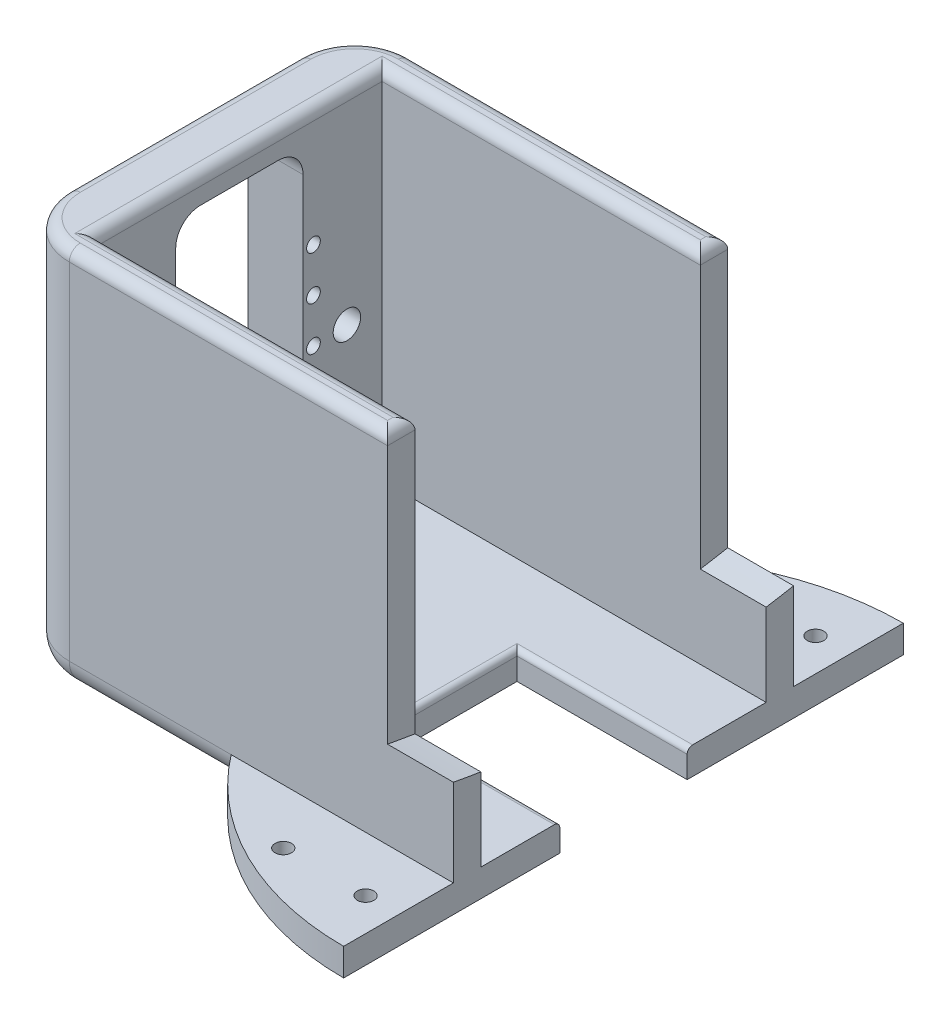
SolidWorks part; units mm, degrees
ref_plane "Plan de face" through (0, 0, 0) normal (0, 0, 1) x (1, 0, 0)
ref_plane "Plan de dessus" through (0, 0, 0) normal (0, 1, 0) x (1, 0, 0)
ref_plane "Plan de droite" through (0, 0, 0) normal (1, 0, 0) x (0, 0, -1)
sketch "Esquisse1" plane through (0, 0, 0) normal (0, 1, 0) x (1, 0, 0)
  line L0 (-50.0182, 0) -> (81.7007, 0) construction
  line L1 (-40.4969, 31) -> (0, 31)
  line L2 (-70, 26) -> (-40.4969, 26)
  line L3 (-70, 26) -> (-70, -26)
  line L4 (0, 31) -> (0, -31)
  line L5 (0, 68.3448) -> (0, -68.3448) construction
  line L6 (-40.4969, 31) -> (-80, 31)
  line L7 (-80, 31) -> (-80, -31)
  line L8 (-80, -31) -> (-40.4969, -31)
  line L9 (-70, -26) -> (-40.4969, -26)
  line L10 (-40.4969, 26) -> (0, 26)
  line L11 (-40.4969, -26) -> (0, -26)
  line L12 (-40.4969, -31) -> (0, -31)
  point P14 (-50, 0)
  dimension "D1" = 80
  dimension "D2" = 62
  dimension "D4" = 10
  dimension "D5" = 5
extrude "Boss.-Extru.5" add sketch "Esquisse1" along normal mid plane 100 contours L9 L3 L2 L6 L7 L8 region at (-20.2485, 0, -29.9879)
sketch "Esquisse5" plane through (-70, 0, 0) normal (1, 0, 0) x (0, 0, -1)
  line L1 (-11.6, -2) -> (11.6, -2)
  line L2 (-11.6, -2) -> (-11.6, -33.8)
  line L3 (-11.6, -33.8) -> (11.6, -33.8)
  line L4 (11.6, -2) -> (11.6, -33.8)
  line L5 (-11.6, -2) -> (-11.6, 5.5)
  line L6 (11.6, -2) -> (11.6, 5.5)
  line L7 (-7.1, 10) -> (7.1, 10)
  arc A0 (-11.6, 5.5) -> (-7.1, 10) centre (-7.1, 5.5) cw
  arc A1 (7.1, 10) -> (11.6, 5.5) centre (7.1, 5.5) cw
  circle A2 centre (0, 0) radius 2.15
  dimension "D3" = 4.3
  dimension "D6" = 4.5
  dimension "D7" = 4.5
  dimension "D1" = 2
  dimension "D2" = 11.6
  dimension "D4" = 43.8
  dimension "D5" = 23.2
  dimension "D8" = 12
extrude "Enlèv. mat.-Extru.1" cut sketch "Esquisse5" against normal blind 10 contours A2 L1 L6 A1 L7 A0 L5 | A2 L1 L2 L3 L4 | L1 A2 | L1 A2 region at (-70, 4.0537, 0) region at (-70, -17.9034, 0) region at (-70, 0.0228, 0) region at (-70, -2.0602, 0)
sketch "Esquisse8" plane through (0, -50, 0) normal (0, 1, 0) x (1, 0, 0)
  line L0 (0, -51) -> (0, 51)
  line L1 (-40.5, -31) -> (-80, -31)
  line L2 (-80, -31) -> (-80, 31)
  line L3 (-80, 31) -> (-40.5, 31)
  line L4 (0, -26) -> (0, -31) construction
  line L5 (-80, -31) -> (0, -31) construction
  line L6 (-80, 0) -> (-0.0031, 0) construction
  arc A1 (0, -51) -> (-40.5, -31) centre (-0.0031, 0) cw
  arc A3 (-40.5, 31) -> (0, 51) centre (-0.0031, 0) cw
  dimension "D1" = 51
  dimension "D2" = 51
  dimension "D3" = 40.5
  dimension "D4" = 20
extrude "Boss.-Extru.6" add sketch "Esquisse8" against normal blind 5
sketch "Esquisse9" plane through (0, 0, 0) normal (1, 0, 0) x (0, 0, -1)
  line L1 (31, 50) -> (31, -50) construction
  line L2 (-31, 50) -> (31, 50)
  line L3 (-31, 50) -> (-31, 15)
  line L4 (-31, 15) -> (31, 15)
  line L8 (0, -5.2261) -> (0, 54.1477) construction
  line L9 (31, 50) -> (31, 15)
  line L10 (-7.1, 10) -> (7.1, 10) construction
  dimension "D1" = 5
sketch "Esquisse11" plane through (-70, 0, 0) normal (1, 0, 0) x (0, 0, -1)
  line L0 (0, 0) -> (0, -23.2285) construction
  line L1 (-11.6, -2) -> (-11.6, -33.8) construction
  line L3 (26, -50) -> (-26, -50) construction
  circle A0 centre (-19.6, -22.214) radius 2.5
  circle A1 centre (19.6, -22.214) radius 2.5
  circle A2 centre (0, 126.5) radius 150
  point P6 (0, -23.5)
  dimension "D1" = 300
  dimension "D3" = 5
  dimension "D2" = 23.5
  dimension "D4" = 8
  dimension "D5" = 39.2
  dimension "D6" = 27.786
extrude "Enlèv. mat.-Extru.9" cut sketch "Esquisse11" against normal blind 5 contours A0 | A1
fillet "Congé1" radius 10 2 edges at (-80, -2.5, 31) (-80, -2.5, -31)
sketch "Esquisse10" plane through (0, 0, 0) normal (1, 0, 0) x (0, 0, -1)
  line L0 (85.2632, 65.694) -> (136.2871, 33.4867)
  line L1 (0, 23.2055) -> (0, -37) construction
  line L2 (-136.2871, 33.4867) -> (-85.2632, 65.694)
  line L3 (85.2632, 65.694) -> (136.2871, 33.4867) construction
  arc A0 (-85.2632, 65.694) -> (85.2632, 65.694) centre (0, 130) ccw
  arc A1 (-136.2871, 33.4867) -> (136.2871, 33.4867) centre (0, 130) ccw
  arc A3 (-73.5134, 52.5348) -> (49.5522, 35.3974) centre (0, 130) ccw
  point P0 (0, 23.2055)
  dimension "D3" = 37
  dimension "D7" = 167
  dimension "D10" = 11.7498
extrude "Enlèv. mat.-Extru.12" cut sketch "Esquisse10" against normal blind 12 contours L2 A1 L0 A0 | A1 | A1 region at (0, 10.5265, 0)
sketch "Esquisse12" plane through (0, -55, 0) normal (0, -1, 0) x (-1, 0, 0)
  line L0 (5.4841, 0) -> (-5.4841, 0) construction
  line L8 (31, -11.6) -> (0, -11.6)
  line L9 (31, -11.6) -> (31, 11.6)
  line L10 (31, 11.6) -> (0, 11.6)
  line L11 (0, -11.6) -> (0, 11.6)
  line L12 (0, -51) -> (0, 51) construction
  dimension "D2" = 23.2
  dimension "D10" = 31
extrude "Enlèv. mat.-Extru.13" cut sketch "Esquisse12" against normal blind 10
fillet "Congé2" radius 1 3 edges at (-15.5, -50, -11.6) (-31, -50, 0) (-15.5, -50, 11.6)
extrude "Enlèv. mat.-Extru.14" cut sketch "Esquisse9" against normal through all
fillet "Congé3" radius 5 5 edges at (-55.25, -55, 31) (-77.0711, -55, 28.0711) (-80, -55, 0) (-77.0711, -55, -28.0711) (-55.25, -55, -31)
fillet "Congé4" radius 2 10 edges at (-12, 15, -28.5) (-41, 15, -26) (-41, 15, -31) (-77.0711, 15, -28.0711) (-80, 15, 0) (-77.0711, 15, 28.0711) (-70, 15, 0) (-41, 15, 26) (-41, 15, 31) (-12, 15, 28.5)
sketch "Esquisse13" plane through (0, -50, 0) normal (0, 1, 0) x (1, 0, 0)
  line L0 (0, 41) -> (-30.3346, 41) construction
  line L1 (0, 31) -> (0, 51) construction
  line L2 (0, 0) -> (-93.9493, 0) construction
  line L3 (0, -41) -> (-30.3346, -41) construction
  arc A0 (0, 51) -> (-40.5, 31) centre (-0.0031, 0) ccw construction
  circle A1 centre (-21, 41) radius 1.5
  circle A2 centre (-6, 41) radius 1.5
  circle A3 centre (-6, -41) radius 1.5
  circle A4 centre (-21, -41) radius 1.5
  dimension "D1" = 3
  dimension "D2" = 15
  dimension "D3" = 6
extrude "Enlèv. mat.-Extru.15" cut sketch "Esquisse13" against normal through all
sketch "Esquisse14" plane through (-70, 0, 0) normal (1, 0, 0) x (0, 0, -1)
  line L1 (0, 0) -> (0, -33.0017) construction
  circle A0 centre (-13.5, -6.5) radius 1.25
  circle A1 centre (-13.5, -14.5) radius 1.25
  circle A2 centre (-13.5, -22.5) radius 1.25
  circle A3 centre (-13.5, -30.5) radius 1.25
  circle A4 centre (13.5, -30.5) radius 1.25
  circle A5 centre (13.5, -22.5) radius 1.25
  circle A6 centre (13.5, -14.5) radius 1.25
  circle A7 centre (13.5, -6.5) radius 1.25
  dimension "D1" = 2.5
  dimension "D2" = 8
  dimension "D3" = 13.5
  dimension "D4" = 8
  dimension "D5" = 8
  dimension "D6" = 6.5
hole_wizard "Trou taraudé M31" positions "Esquisse3D1" profile "Esquisse15" tap size "M3" standard "Iso"
sketch3d "Esquisse3D1"
  point P0 (-70, -6.5, 13.5)
  point P3 (-70, -6.5, -13.5)
  point P6 (-70, -14.5, -13.5)
  point P9 (-70, -14.5, 13.5)
  point P12 (-70, -22.5, 13.5)
  point P15 (-70, -22.5, -13.5)
  point P17 (-70, -30.5, -13.5)
  point P19 (-70, -30.5, 13.5)
sketch "Esquisse15" plane through (-70, -6.5, 13.5) normal (0, 1, 0) x (0, 0, -1)
  line L0 (0, 0) -> (0, 13.2511)
  line L1 (0, 13.2511) -> (1.25, 12.5)
  line L2 (1.25, 12.5) -> (1.25, 0)
  line L5 (1.25, 0) -> (0, 0)
  line L10 (0, 13.2511) -> (-1.25, 12.5) construction
  line L11 (0, -6.35) -> (0, 107.95) construction
  dimension "Diamètre du trou pour taraudage" = 2.5
  dimension "Profondeur du trou pour taraudage" = 12.5
  dimension "Angle de pointe" = 118
cosmetic thread "Filetage de perçage1" parameters "D1"=10, "D2"=3
cosmetic thread "Filetage de perçage2" parameters "D1"=10, "D2"=3
cosmetic thread "Filetage de perçage3" parameters "D1"=10, "D2"=3
cosmetic thread "Filetage de perçage4" parameters "D1"=10, "D2"=3
cosmetic thread "Filetage de perçage5" parameters "D1"=10, "D2"=3
cosmetic thread "Filetage de perçage6" parameters "D1"=10, "D2"=3
cosmetic thread "Filetage de perçage7" parameters "D1"=10, "D2"=3
cosmetic thread "Filetage de perçage8" parameters "D1"=10, "D2"=3
